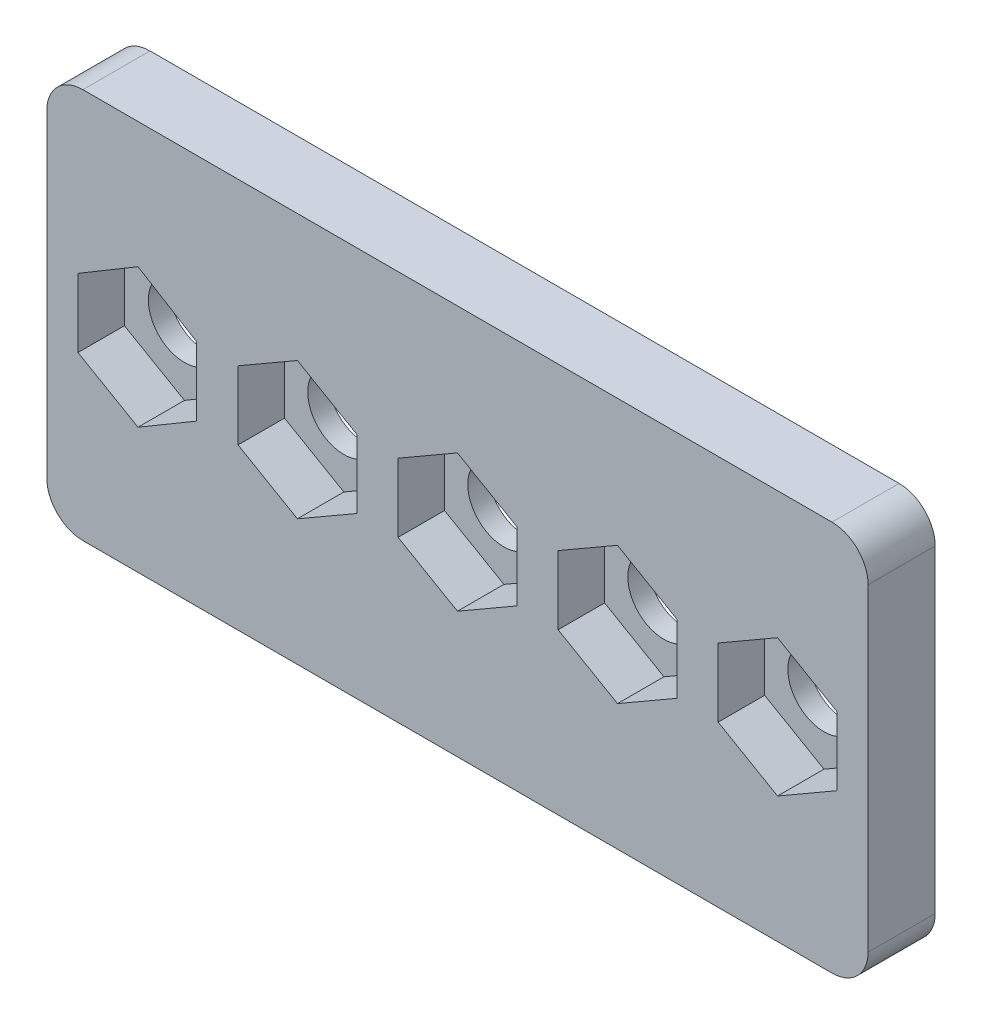
SolidWorks part; units mm, degrees
ref_plane "Front Plane" through (0, 0, 0) normal (0, 0, 1) x (1, 0, 0)
ref_plane "Top Plane" through (0, 0, 0) normal (0, 1, 0) x (1, 0, 0)
ref_plane "Right Plane" through (0, 0, 0) normal (1, 0, 0) x (0, 0, -1)
sketch "Sketch3" plane through (0, 0, 6.8) normal (0, 0, 1) x (1, 0, 0)
  line L0 (-33.5665, 13.4163) -> (-33.5665, 25.5958)
  line L1 (-33.5665, 6.6277) -> (-18.1293, 6.6277)
  line L2 (-18.1293, 6.6277) -> (-2.6293, 6.6277)
  line L3 (-2.6293, 6.6277) -> (12.8707, 6.6277)
  line L4 (12.8707, 6.6277) -> (28.3707, 6.6277)
  line L6 (-33.5665, -0.0481) -> (-33.5665, -12.2276)
  line L7 (-33.5665, -0.0481) -> (-27.8793, 3.3079)
  line L8 (-27.8793, 3.3079) -> (-27.8793, 9.9474)
  line L9 (-27.8793, 9.9474) -> (-33.5665, 13.4163)
  line L10 (-33.5665, 13.4163) -> (-39.3793, 9.9474)
  line L11 (-39.3793, 9.9474) -> (-39.3793, 3.3079)
  line L12 (-39.3793, 3.3079) -> (-33.5665, -0.0481)
  line L13 (-18.1293, 13.2672) -> (-23.8793, 9.9474)
  line L14 (-23.8793, 9.9474) -> (-23.8793, 3.3079)
  line L15 (-23.8793, 3.3079) -> (-18.1293, -0.0119)
  line L16 (-18.1293, -0.0119) -> (-12.3793, 3.3079)
  line L17 (-12.3793, 3.3079) -> (-12.3793, 9.9474)
  line L18 (-12.3793, 9.9474) -> (-18.1293, 13.2672)
  line L19 (-2.6293, 13.2672) -> (-8.3793, 9.9474)
  line L20 (-8.3793, 9.9474) -> (-8.3793, 3.3079)
  line L21 (-8.3793, 3.3079) -> (-2.6293, -0.0119)
  line L22 (-2.6293, -0.0119) -> (3.1207, 3.3079)
  line L23 (3.1207, 3.3079) -> (3.1207, 9.9474)
  line L24 (3.1207, 9.9474) -> (-2.6293, 13.2672)
  line L25 (12.8707, 13.2672) -> (7.1207, 9.9474)
  line L26 (7.1207, 9.9474) -> (7.1207, 3.3079)
  line L27 (7.1207, 3.3079) -> (12.8707, -0.0119)
  line L28 (12.8707, -0.0119) -> (18.6207, 3.3079)
  line L29 (18.6207, 3.3079) -> (18.6207, 9.9474)
  line L30 (18.6207, 9.9474) -> (12.8707, 13.2672)
  line L31 (28.3707, 13.2672) -> (22.6207, 9.9474)
  line L32 (22.6207, 9.9474) -> (22.6207, 3.3079)
  line L33 (22.6207, 3.3079) -> (28.3707, -0.0119)
  line L34 (28.3707, -0.0119) -> (34.1207, 3.3079)
  line L35 (34.1207, 3.3079) -> (34.1207, 9.9474)
  line L36 (34.1207, 9.9474) -> (28.3707, 13.2672)
  line L39 (-39.3793, 6.6277) -> (-42.4022, 6.6841)
  line L40 (-42.4022, 25.5958) -> (37.1437, 25.5958)
  line L41 (-42.4022, 25.5958) -> (-42.4022, -12.2276)
  line L42 (-42.4022, -12.2276) -> (37.1437, -12.2276)
  line L43 (37.1437, 25.5958) -> (37.1437, -12.2276)
  line L44 (34.1207, 6.6277) -> (37.1437, 6.6841)
  circle A0 centre (-33.5665, 6.6277) radius 3.5
  circle A1 centre (-18.1293, 6.6277) radius 3.5
  circle A2 centre (-2.6293, 6.6277) radius 3.5
  circle A3 centre (12.8707, 6.6277) radius 3.5
  circle A4 centre (28.3707, 6.6277) radius 3.5
  circle A5 centre (-33.5665, 6.6277) radius 5.7494 construction
  circle A6 centre (-18.1293, 6.6277) radius 5.75 construction
  circle A7 centre (-2.6293, 6.6277) radius 5.75 construction
  circle A8 centre (12.8707, 6.6277) radius 5.75 construction
  circle A9 centre (28.3707, 6.6277) radius 5.75 construction
  dimension "D1" = 13.2791
  dimension "D2" = 11.5
extrude "Boss-Extrude2" add sketch "Sketch3" against normal blind 6.5 contours L35 L44 L43 L40 L0 L9 L8 L1 L14 L13 L18 L17 L2 L20 L19 L24 L23 L3 L26 L25 L30 L29 L4 L32 L31 L36 | A4 L32 L33 L34 L35 L36 L31 | A3 L4 L29 L30 L25 L26 L3 | A2 L3 L23 L24 L19 L20 L2 | A1 L2 L17 L18 L13 L14 L1 | A0 L8 L9 L10 L11 L12 L7 | L40 L41 L39 L11 L10 L0 | L41 L42 L6 L12 L11 L39 | L44 L35 L34 L33 L32 L4 L29 L28 L27 L26 L3 L23 L22 L21 L20 L2 L17 L16 L15 L14 L1 L8 L7 L6 L42 L43 | A1 L1 L14 L15 L16 L17 L2 | A2 L2 L20 L21 L22 L23 L3 | A3 L3 L26 L27 L28 L29 L4 region at (-38.3744, 17.5761, 6.8) region at (1.9526, 17.7538, 6.8) region at (-30.8151, 11.5307, 6.8) region at (1.9492, -4.4373, 6.8) region at (-38.3741, -4.2368, 6.8) region at (-23.7465, 8.2876, 6.8) region at (-22.7543, 6.4949, 6.8) region at (33.9451, 4.9678, 6.8) region at (-8.2465, 8.2876, 6.8) region at (-7.2543, 6.4949, 6.8) region at (18.4879, 4.9678, 6.8) region at (17.4957, 6.7605, 6.8)
extrude "Cut-Extrude2" cut sketch "Sketch3<3>" against normal blind 4.5 contours A0 L8 L9 L10 L11 L12 L7 | A1 L2 L17 L18 L13 L14 L1 | A1 L1 L14 L15 L16 L17 L2 | A2 L3 L23 L24 L19 L20 L2 | A2 L2 L20 L21 L22 L23 L3 | A3 L4 L29 L30 L25 L26 L3 | A3 L3 L26 L27 L28 L29 L4 | A4 L32 L33 L34 L35 L36 L31 region at (-30.8151, 11.5307, 6.8) region at (-23.7465, 8.2876, 6.8) region at (-22.7543, 6.4949, 6.8) region at (33.9451, 4.9678, 6.8) region at (-8.2465, 8.2876, 6.8) region at (-7.2543, 6.4949, 6.8) region at (18.4879, 4.9678, 6.8) region at (17.4957, 6.7605, 6.8)
sketch "Sketch3<3>" plane through (0, 0, 6.8) normal (0, 0, 1) x (1, 0, 0) same geometry as "Sketch3"
fillet "Fillet1" radius 3.5 4 edges at (-42.4022, 25.5958, 3.55) (-42.4022, -12.2276, 3.55) (37.1437, 25.5958, 3.55) (37.1437, -12.2276, 3.55)
